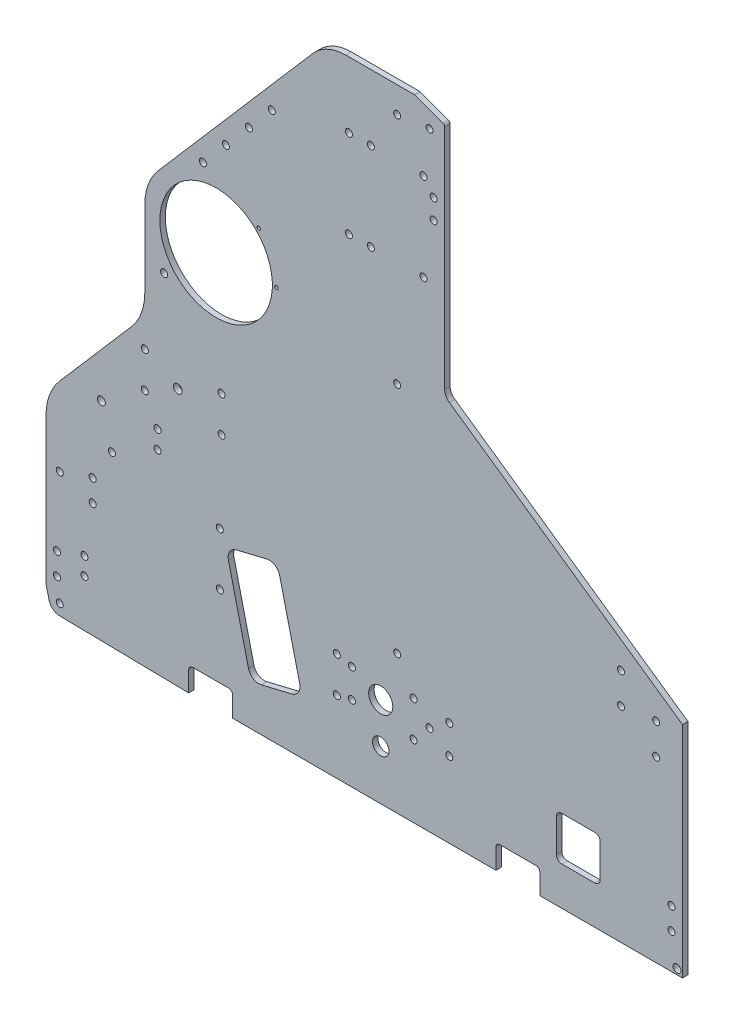
SolidWorks part; units mm, degrees
ref_plane "Front Plane" through (0, 0, 0) normal (0, 0, 1) x (1, 0, 0)
ref_plane "Top Plane" through (0, 0, 0) normal (0, 1, 0) x (1, 0, 0)
ref_plane "Right Plane" through (0, 0, 0) normal (1, 0, 0) x (0, 0, -1)
sketch "Sketch1" plane through (0, 0, 0) normal (0, 0, 1) x (1, 0, 0)
  line L0 (82.55, -20.32) -> (82.55, -6.35)
  line L2 (0, 0) -> (0, 157.48)
  line L4 (368.3, -20.32) -> (368.3, 106.68)
  line L5 (82.55, -6.35) -> (107.95, -6.35)
  line L6 (107.95, -6.35) -> (107.95, -20.32)
  line L7 (107.95, -20.32) -> (260.35, -20.32)
  line L8 (260.35, -20.32) -> (260.35, -6.35)
  line L9 (260.35, -6.35) -> (285.75, -6.35)
  line L10 (285.75, -6.35) -> (285.75, -20.32)
  line L11 (285.75, -20.32) -> (368.3, -20.32)
  line L12 (361.95, 12.7) -> (368.3, 12.7) construction
  line L13 (0, 0) -> (6.35, 0) construction
  line L14 (0.1896, -7.8901) -> (1.7771, -14.2401)
  line L15 (7.8295, -19.0491) -> (82.55, -20.32)
  line L16 (0, 0) -> (0, -6.35)
  line L17 (76.2, 128.905) -> (79.375, 128.905) construction
  line L18 (57.15, 118.5863) -> (101.6, 118.5862) construction
  line L19 (57.15, 118.5863) -> (57.15, 139.2238) construction
  line L20 (101.6, 118.5862) -> (101.6, 139.2237) construction
  line L21 (57.15, 139.2238) -> (101.6, 139.2237) construction
  line L22 (57.15, 118.5863) -> (101.6, 139.2237) construction
  line L23 (101.6, 118.5862) -> (57.15, 139.2238) construction
  line L25 (203.2, 59.805) -> (203.2, 194.805) construction
  line L26 (203.2, 194.805) -> (203.2, 329.805) construction
  line L27 (355.6, 332.105) -> (330.2, 332.105) construction
  line L28 (330.2, 332.105) -> (330.2, 217.805) construction
  line L29 (330.2, 217.805) -> (355.6, 217.805) construction
  line L30 (355.6, 217.805) -> (355.6, 332.105) construction
  line L31 (203.2, 344.805) -> (203.2, 194.805) construction
  line L32 (50.8, 332.105) -> (76.2, 332.105) construction
  line L33 (76.2, 332.105) -> (76.2, 217.805) construction
  line L34 (50.8, 217.805) -> (50.8, 332.105) construction
  line L35 (76.2, 217.805) -> (50.8, 217.805) construction
  line L36 (213.2, 344.805) -> (230.6638, 338.455)
  line L37 (203.2, 344.805) -> (161.925, 344.805)
  line L38 (203.2, 344.805) -> (213.2, 344.805)
  line L39 (348.5362, 344.805) -> (413.4623, 344.805)
  line L40 (348.5362, 344.805) -> (230.6638, 344.805) construction
  line L42 (161.925, 344.805) -> (0, 157.48)
  line L44 (230.6638, 338.455) -> (230.6638, 202.565)
  line L45 (230.6638, 202.565) -> (368.3, 106.68)
  line L46 (213.2, 344.805) -> (-141.0713, 344.805) construction
  circle A0 centre (6.35, 0) radius 2.032
  circle A1 centre (6.35, 12.7) radius 2.032
  circle A2 centre (361.95, 0) radius 2.032
  circle A3 centre (361.95, 12.7) radius 2.032
  arc A5 (1.7771, -14.2401) -> (7.8295, -19.0491) centre (7.9375, -12.7) ccw
  circle A6 centre (7.9375, -12.7) radius 2.032
  arc A7 (0, -6.35) -> (0.1896, -7.8901) centre (6.35, -6.35) ccw
  circle A8 centre (38.1, 78.105) radius 2.032
  circle A9 centre (76.2, 128.905) radius 2.54
  circle A10 centre (101.6, 118.5862) radius 2.032
  circle A11 centre (101.6, 139.2237) radius 2.032
  circle A12 centre (57.15, 139.2238) radius 2.032
  circle A13 centre (57.15, 118.5863) radius 2.032
  circle A15 centre (203.2, 59.805) radius 2
  circle A16 centre (203.2, 194.805) radius 2
  circle A17 centre (203.2, 329.805) radius 2
  circle A18 centre (63.5, 313.055) radius 2.032
  circle A20 centre (355.6, 332.105) radius 2.032
  circle A21 centre (330.2, 332.105) radius 2.032
  circle A22 centre (355.6, 217.805) radius 2.032
  circle A23 centre (330.2, 217.805) radius 2.032
  circle A24 centre (50.8, 332.105) radius 2.032
  circle A25 centre (76.2, 332.105) radius 2.032
  circle A26 centre (50.8, 217.805) radius 2.032
  circle A27 centre (76.2, 217.805) radius 2.032
  circle A28 centre (221.9319, 332.105) radius 2
  circle A29 centre (224.3138, 298.831) radius 2.032
  circle A30 centre (353.06, 100.7351) radius 2.032
  circle A31 centre (332.74, 115.9751) radius 2.032
  circle A32 centre (332.74, 98.1951) radius 2.032
  circle A33 centre (353.06, 82.9551) radius 2.032
  circle A34 centre (117.3562, 280.4276) radius 2.032
  circle A35 centre (104.0678, 265.0548) radius 2.032
  circle A36 centre (90.7795, 249.682) radius 2.032
  circle A38 centre (130.6445, 295.8004) radius 2.032
  circle A39 centre (68.326, 182.9237) radius 2.032
  circle A40 centre (224.3138, 287.401) radius 2.032
  point P82 (203.2, 344.805)
  point P83 (221.9319, 341.63)
  point P90 (368.3, 62.484)
  dimension "D6" = 4.064
  dimension "D10" = 6.35
  dimension "D11" = 4.064
  dimension "D17" = 38.1
  dimension "D27" = 4
  dimension "D31" = 4.064
  dimension "D32" = 41.275
  dimension "D36" = 4.064
  dimension "D47" = 39.624
  dimension "D48" = 4.064
  dimension "D25" = 5.08
  dimension "D26" = 4.064
  dimension "D52" = 4.064
  dimension "D65" = 4.064
  dimension "D2" = 127
  dimension "D3" = 13.97
  dimension "D4" = 25.4
  dimension "D5" = 152.4
  dimension "D7" = 12.7
  dimension "D8" = 6.35
  dimension "D9" = 20.32
  dimension "D12" = 12.7
  dimension "D13" = 1.5875
  dimension "D14" = 82.55
  dimension "D15" = 368.3
  dimension "D16" = 6.35
  dimension "D18" = 98.425
  dimension "D19" = 38.1
  dimension "D20" = 50.8
  dimension "D21" = 3.175
  dimension "D22" = 270
  dimension "D23" = 20.6375
  dimension "D24" = 44.45
  dimension "D28" = 135
  dimension "D29" = 12.7
  dimension "D30" = 15
  dimension "D33" = 63.5
  dimension "D34" = 27.4638
  dimension "D35" = 12.7
  dimension "D37" = 114.3
  dimension "D38" = 25.4
  dimension "D39" = 12.7
  dimension "D40" = 157.48
  dimension "D41" = 142.24
  dimension "D42" = 365.125
  dimension "D43" = 10
  dimension "D44" = 6.35
  dimension "D45" = 31.75
  dimension "D46" = 6.35
  dimension "D49" = 6.35
  dimension "D50" = 203.2
  dimension "D51" = 15.24
  dimension "D53" = 17.78
  dimension "D54" = 17.78
  dimension "D55" = 20.32
  dimension "D56" = 15.24
  dimension "D57" = 92.202
  dimension "D58" = 8.382
  dimension "D59" = 20.32
  dimension "D60" = 20.32
  dimension "D61" = 8.382
  dimension "D62" = 20.32
  dimension "D63" = 8.382
  dimension "D64" = 8.382
  dimension "D66" = 35.052
  dimension "D67" = 68.326
  dimension "D68" = 11.43
extrude "Boss-Extrude1" add sketch "Sketch1" along normal blind 3.175 contours L16 A7 L14 A5 L15 L2 A0 A1 A6 region at (171.3489, 119.5343, 0)
fillet "Fillet1" radius 2.286 4 edges at (285.75, -6.35, 1.5875) (107.95, -6.35, 1.5875) (260.35, -6.35, 1.5875) (82.55, -6.35, 1.5875)
fillet "Fillet2" radius 6.35 1 edges at (230.6638, 202.565, 1.5875)
sketch "Sketch2" plane through (0, 0, 0) normal (0, 0, -1) x (-1, 0, 0)
  circle A0 centre (-100.5528, 71.086) radius 2.032 construction
  circle A1 centre (-100.5528, 40.606) radius 2.032 construction
  circle A2 centre (-22.225, 18.2025) radius 2.032 construction
  circle A3 centre (-22.225, 8.0425) radius 2.032 construction
  circle A4 centre (-100.5528, 71.086) radius 2.032
  circle A5 centre (-100.5528, 40.606) radius 2.032
  circle A6 centre (-22.225, 18.2025) radius 2.032
  circle A7 centre (-22.225, 8.0425) radius 2.032
extrude "Cut-Extrude1" cut sketch "Sketch2" against normal through all
fillet "Fillet3" radius 1.5875 2 edges at (230.6638, 338.455, 1.5875) (213.2, 344.805, 1.5875)
sketch "Sketch3" plane through (0, 0, 3.175) normal (0, 0, 1) x (1, 0, 0)
  line L0 (132.9524, 63.2646) -> (132.7215, 64.2281) construction
  line L1 (128.3814, 66.8897) -> (110.6828, 62.6472) construction
  line L2 (114.5132, 58.4237) -> (126.8822, 61.3887) construction
  line L3 (108.0212, 58.3071) -> (108.2522, 57.3436) construction
  line L4 (131.2006, 57.703) -> (140.0164, 20.9265) construction
  line L5 (144.0993, 16.7636) -> (132.9524, 63.2646) construction
  line L6 (108.2522, 57.3436) -> (119.3991, 10.8426) construction
  line L7 (121.1509, 16.4042) -> (112.3351, 53.1807) construction
  line L8 (119.3991, 10.8426) -> (119.6301, 9.8791) construction
  line L9 (144.3303, 15.8001) -> (144.0993, 16.7636) construction
  line L10 (137.8383, 15.6835) -> (125.4694, 12.7185) construction
  line L11 (123.9701, 7.2175) -> (141.6687, 11.4601) construction
  line L12 (132.9524, 63.2646) -> (132.7215, 64.2281)
  line L13 (128.3814, 66.8897) -> (110.6828, 62.6472)
  line L14 (114.5132, 58.4237) -> (126.8822, 61.3887)
  line L15 (108.0212, 58.3071) -> (108.2522, 57.3436)
  line L16 (131.2006, 57.703) -> (140.0164, 20.9265)
  line L17 (144.0993, 16.7636) -> (132.9524, 63.2646)
  line L18 (108.2522, 57.3436) -> (119.3991, 10.8426)
  line L19 (121.1509, 16.4042) -> (112.3351, 53.1807)
  line L20 (119.3991, 10.8426) -> (119.6301, 9.8791)
  line L21 (144.3303, 15.8001) -> (144.0993, 16.7636)
  line L22 (137.8383, 15.6835) -> (125.4694, 12.7185)
  line L23 (123.9701, 7.2175) -> (141.6687, 11.4601)
  line L24 (127.7894, 69.3598) -> (110.0908, 65.1172)
  line L25 (105.5512, 57.715) -> (105.7822, 56.7515)
  line L26 (105.7822, 56.7515) -> (116.9291, 10.2505)
  line L27 (116.9291, 10.2505) -> (117.16, 9.287)
  line L28 (124.5622, 4.7475) -> (142.2608, 8.99)
  line L29 (146.8003, 16.3922) -> (146.5694, 17.3557)
  line L30 (146.5694, 17.3557) -> (135.4225, 63.8567)
  line L31 (135.4225, 63.8567) -> (135.1915, 64.8202)
  line L32 (14.605, -0.1369) -> (103.7278, 32.3011) construction
  line L33 (14.605, -0.1369) -> (103.7278, 32.3011)
  line L35 (-39.6666, 74.7152) -> (103.7278, 126.9065) construction
  arc A0 (132.7215, 64.2281) -> (128.6308, 66.9403) centre (129.2206, 63.3889) ccw construction
  arc A1 (110.6828, 62.6472) -> (110.4377, 62.5791) centre (111.522, 59.1463) ccw construction
  arc A2 (128.6308, 66.9403) -> (128.3814, 66.8897) centre (129.2206, 63.3889) ccw construction
  arc A3 (110.4377, 62.5791) -> (108.0212, 58.3071) centre (111.522, 59.1463) ccw construction
  arc A4 (119.6301, 9.8791) -> (123.7207, 7.1669) centre (123.1309, 10.7183) ccw construction
  arc A5 (141.9139, 11.5281) -> (144.3303, 15.8001) centre (140.8295, 14.9609) ccw construction
  arc A6 (141.6687, 11.4601) -> (141.9139, 11.5281) centre (140.8295, 14.9609) ccw construction
  arc A7 (123.7207, 7.1669) -> (123.9701, 7.2175) centre (123.1309, 10.7183) ccw construction
  arc A8 (132.7215, 64.2281) -> (128.6308, 66.9403) centre (129.2206, 63.3889) ccw
  arc A9 (110.6828, 62.6472) -> (110.4377, 62.5791) centre (111.522, 59.1463) ccw
  arc A10 (128.6308, 66.9403) -> (128.3814, 66.8897) centre (129.2206, 63.3889) ccw
  arc A11 (110.4377, 62.5791) -> (108.0212, 58.3071) centre (111.522, 59.1463) ccw
  arc A12 (119.6301, 9.8791) -> (123.7207, 7.1669) centre (123.1309, 10.7183) ccw
  arc A13 (141.9139, 11.5281) -> (144.3303, 15.8001) centre (140.8295, 14.9609) ccw
  arc A14 (141.6687, 11.4601) -> (141.9139, 11.5281) centre (140.8295, 14.9609) ccw
  arc A15 (123.7207, 7.1669) -> (123.9701, 7.2175) centre (123.1309, 10.7183) ccw
  arc A16 (110.0908, 65.1172) -> (109.6726, 65.0012) centre (111.522, 59.1463) ccw
  arc A17 (109.6726, 65.0012) -> (105.5512, 57.715) centre (111.522, 59.1463) ccw
  arc A18 (117.16, 9.287) -> (124.1369, 4.6613) centre (123.1309, 10.7183) ccw
  arc A19 (124.1369, 4.6613) -> (124.5622, 4.7475) centre (123.1309, 10.7183) ccw
  arc A20 (142.2608, 8.99) -> (142.6789, 9.1061) centre (140.8295, 14.9609) ccw
  arc A21 (142.6789, 9.1061) -> (146.8003, 16.3922) centre (140.8295, 14.9609) ccw
  arc A22 (135.1915, 64.8202) -> (128.2147, 69.446) centre (129.2206, 63.3889) ccw
  arc A23 (128.2147, 69.446) -> (127.7894, 69.3598) centre (129.2206, 63.3889) ccw
  circle A24 centre (64.5259, 102.9405) radius 2.032 construction
  circle A25 centre (64.5259, 92.5258) radius 2.032 construction
  circle A26 centre (133.35, 208.2281) radius 1.016 construction
  circle A33 centre (26.9875, 46.9531) radius 2.032
  circle A34 centre (26.9875, 59.6531) radius 2.032
  circle A35 centre (7.9375, 53.3031) radius 2.032
  circle A36 centre (7.9375, 53.3031) radius 2.032 construction
  circle A37 centre (32.0306, 100.8109) radius 31.75 construction
  circle A38 centre (32.0306, 100.8109) radius 2.286
  circle A39 centre (123.1207, 232.9238) radius 1.016 construction
  circle A40 centre (64.5259, 102.9405) radius 2.032
  circle A41 centre (64.5259, 92.5258) radius 2.032
  circle A42 centre (133.35, 208.2281) radius 1.016
  circle A43 centre (123.1207, 232.9238) radius 1.016
  circle A44 centre (26.9875, 59.6531) radius 2.032 construction
  circle A45 centre (26.9875, 46.9531) radius 2.032 construction
  ellipse E0 centre (124.5974, 48.8487) end of major axis (128.5376, 61.3578) minor radius 6 (131.2006, 57.703) -> (126.8822, 61.3887) ccw construction
  ellipse E1 centre (122.2349, 48.2824) end of major axis (113.0518, 57.6456) minor radius 6 (114.5132, 58.4237) -> (112.3351, 53.1807) ccw construction
  ellipse E2 centre (127.7541, 25.2585) end of major axis (131.6942, 37.7675) minor radius 6 (121.1509, 16.4042) -> (125.4694, 12.7185) ccw construction
  ellipse E3 centre (130.1166, 25.8248) end of major axis (139.2998, 16.4616) minor radius 6 (137.8383, 15.6835) -> (140.0164, 20.9265) ccw construction
  ellipse E4 centre (124.5974, 48.8487) end of major axis (128.5376, 61.3578) minor radius 6 (131.2006, 57.703) -> (126.8822, 61.3887) ccw
  ellipse E5 centre (122.2349, 48.2824) end of major axis (131.4181, 38.9192) minor radius 6 (114.5132, 58.4237) -> (112.3351, 53.1807) ccw
  ellipse E6 centre (127.7541, 25.2585) end of major axis (123.8139, 12.7495) minor radius 6 (121.1509, 16.4042) -> (125.4694, 12.7185) ccw
  ellipse E7 centre (130.1166, 25.8248) end of major axis (139.2998, 16.4616) minor radius 6 (137.8383, 15.6835) -> (140.0164, 20.9265) ccw
  point P115 (32.0306, 100.8109)
  dimension "D3" = 63.5
  dimension "D4" = 4.572
  dimension "D2" = 88.9
  dimension "D1" = 2.54
extrude "Cut-Extrude2" cut sketch "Sketch3" against normal through all contours A22 A23 L24 A16 A17 L25 L26 L27 A18 A19 L28 A20 A21 L29 L30 L31 A15 A12 L20 L18 L15 A11 A9 L13 A10 A8 L12 L17 L21 A13 A14 L23 | A12 A15 L23 A14 A13 L21 L17 L12 A8 A10 L13 A9 A11 L15 L18 L20 E7 L22 E6 L19 E5 L14 E4 L16 | L22 E7 L16 E4 L14 E5 L19 E6 | A38 | A41 | A40 | A35 | A34 | A33 | A43 | A42 region at (137.844, 39.8506, 3.175) region at (126.1758, 37.0536, 3.175) region at (128.1544, 68.6507, 3.175) region at (32.0306, 100.8109, 3.175) region at (64.5259, 102.9405, 3.175) region at (64.5259, 92.5258, 3.175)
sketch "Sketch4" plane through (0, 0, 3.175) normal (0, 0, 1) x (1, 0, 0)
  line L0 (57.15, 139.2238) -> (101.6, 139.2237) construction
  line L1 (168.275, 21.4312) -> (212.725, 21.4312) construction
  line L2 (168.275, 21.4312) -> (168.275, 42.0687) construction
  line L3 (168.275, 42.0687) -> (212.725, 42.0687) construction
  line L4 (212.725, 21.4312) -> (212.725, 42.0687) construction
  line L5 (168.275, 21.4312) -> (212.725, 42.0687) construction
  line L6 (168.275, 42.0687) -> (212.725, 21.4312) construction
  line L7 (57.15, 118.5863) -> (57.15, 139.2238) construction
  line L8 (107.95, -20.32) -> (260.35, -20.32) construction
  line L9 (193.675, 31.75) -> (177.005, 31.75) construction
  line L10 (190.5, 31.75) -> (193.675, 31.75) construction
  line L11 (6.35, 12.7) -> (361.95, 12.7) construction
  line L12 (107.95, -6.35) -> (107.95, -20.32) construction
  line L13 (193.675, 31.75) -> (220.6625, 31.75) construction
  line L14 (177.005, 23.4569) -> (177.005, 40.0431) construction
  line L15 (213.2, 44.805) -> (193.2, 44.805) construction
  line L16 (213.2, 44.805) -> (213.2, 344.805) construction
  line L17 (213.2, 344.805) -> (193.2, 344.805) construction
  line L18 (193.2, 44.805) -> (193.2, 344.805) construction
  line L19 (213.2, 44.805) -> (193.2, 344.805) construction
  line L20 (213.2, 344.805) -> (193.2, 44.805) construction
  line L21 (226.9319, 332.105) -> (226.9319, 31.75) construction
  line L22 (237.33, 40.0431) -> (233.3612, 40.0431) construction
  line L23 (237.33, 23.4569) -> (233.3612, 23.4569) construction
  circle A0 centre (168.275, 42.0687) radius 2.032
  circle A1 centre (212.725, 42.0687) radius 2.032
  circle A2 centre (212.725, 21.4312) radius 2.032
  circle A3 centre (168.275, 21.4312) radius 2.032
  circle A4 centre (193.675, 31.75) radius 6.985
  circle A7 centre (220.6625, 31.75) radius 14.2875 construction
  circle A8 centre (193.675, 31.75) radius 12.7 construction
  circle A9 centre (177.005, 40.0431) radius 2.032
  circle A10 centre (177.005, 23.4569) radius 2.032
  circle A11 centre (237.33, 40.0431) radius 2.032 construction
  circle A12 centre (237.33, 23.4569) radius 2.032 construction
  circle A13 centre (193.675, 8.4667) radius 4.7625
  circle A14 centre (221.9319, 31.75) radius 2.032
  circle A15 centre (221.9319, 31.75) radius 5 construction
  circle A16 centre (221.9319, 332.105) radius 5 construction
  circle A17 centre (233.3612, 23.4569) radius 2.032
  circle A18 centre (233.3612, 40.0431) radius 2.032
  point P0 (190.5, 31.75)
  point P26 (203.2, 194.805)
  point P38 (177.005, 31.75)
  dimension "D1" = 4.064
  dimension "D4" = 13.97
  dimension "D7" = 9.525
  dimension "D10" = 25.4
  dimension "D11" = 28.575
  dimension "D16" = 10
  dimension "D17" = 4.064
  dimension "D18" = 10
  dimension "D2" = 52.07
  dimension "D3" = 3.175
  dimension "D5" = 82.55
  dimension "D6" = 26.9875
  dimension "D8" = 20
  dimension "D9" = 300
  dimension "D12" = 16.67
  dimension "D13" = 16.5862
  dimension "D14" = 60.325
  dimension "D15" = 23.2833
  dimension "D19" = 3.9688
extrude "Cut-Extrude3" cut sketch "Sketch4" against normal through all
sketch "Sketch5" plane through (0, 0, -187.325) normal (0, 0, -1) x (-1, 0, 0)
  line L0 (-57.15, 223.5947) -> (-57.15, 155.6235)
  line L1 (-161.925, 344.805) -> (-52.7201, 218.4699) construction
  line L2 (-57.15, 155.6235) -> (0, 89.5088)
  line L3 (0, -6.35) -> (0, 157.48) construction
  line L4 (-50.4199, 215.8089) -> (0, 157.48) construction
  line L5 (-50.4199, 215.8089) -> (0, 157.48) construction
  line L6 (-57.15, 223.5947) -> (0, 157.48)
  line L7 (0, 157.48) -> (0, 89.5088)
  circle A0 centre (-98.425, 208.2281) radius 32.5437
  circle A1 centre (-365.125, -17.145) radius 2.286 construction
  circle A2 centre (-365.125, -17.145) radius 2.286
  dimension "D3" = 65.0875
  dimension "D1" = 44.45
  dimension "D2" = 57.15
  dimension "D4" = 41.275
  dimension "D5" = 41.275
extrude "Cut-Extrude5" cut sketch "Sketch5" against normal through all contours A0 | L7 L6 L0 L2 | A2 region at (28.575, 156.5518, -187.325) region at (98.425, 208.2281, -187.325)
fillet "Fillet4" radius 31.75 3 edges at (0, 89.5088, 1.5875) (57.15, 155.6235, 1.5875) (57.15, 223.5947, 1.5875)
sketch "Sketch6" plane through (0, 0, 3.175) normal (0, 0, 1) x (1, 0, 0)
  line L0 (285.75, -20.32) -> (368.3, -20.32) construction
  line L1 (298.45, 27.305) -> (317.5, 27.305)
  line L2 (295.275, 24.13) -> (295.275, 5.08)
  line L3 (298.45, 1.905) -> (317.5, 1.905)
  line L4 (320.675, 24.13) -> (320.675, 5.08)
  line L5 (295.275, 27.305) -> (320.675, 1.905) construction
  line L6 (295.275, 1.905) -> (320.675, 27.305) construction
  line L7 (368.3, -20.32) -> (368.3, 106.68) construction
  arc A0 (295.275, 5.08) -> (298.45, 1.905) centre (298.45, 5.08) ccw
  arc A1 (317.5, 1.905) -> (320.675, 5.08) centre (317.5, 5.08) ccw
  arc A2 (317.5, 27.305) -> (320.675, 24.13) centre (317.5, 24.13) cw
  arc A3 (298.45, 27.305) -> (295.275, 24.13) centre (298.45, 24.13) ccw
  point P0 (307.975, 14.605)
  dimension "D2" = 3.175
  dimension "D1" = 25.4
  dimension "D3" = 22.225
  dimension "D4" = 47.625
extrude "Cut-Extrude6" cut sketch "Sketch6" against normal through all
fillet "Fillet5" radius 25.4 1 edges at (161.925, 344.805, 1.5875)
sketch "Sketch8" plane through (0, 0, 0) normal (0, 0, -1) x (-1, 0, 0)
  circle A0 centre (-187.96, 306.705) radius 2.032 construction
  arc A1 (-176.3652, 304.9998) -> (-176.3652, 308.4102) centre (-175.26, 306.705) ccw construction
  arc A2 (-219.0586, 304.7694) -> (-219.0586, 308.6405) centre (-218.44, 306.705) ccw construction
  circle A3 centre (-205.74, 306.705) radius 2.032 construction
  arc A4 (-219.0586, 253.9694) -> (-219.0586, 257.8405) centre (-218.44, 255.905) ccw construction
  circle A5 centre (-205.74, 255.905) radius 2.032 construction
  circle A6 centre (-187.96, 255.905) radius 2.032 construction
  arc A7 (-176.3652, 254.1998) -> (-176.3652, 257.6102) centre (-175.26, 255.905) ccw construction
  circle A8 centre (-187.96, 306.705) radius 2.032
  arc A9 (-176.3652, 304.9998) -> (-176.3652, 308.4102) centre (-175.26, 306.705) ccw
  arc A10 (-219.0586, 304.7694) -> (-219.0586, 308.6405) centre (-218.44, 306.705) ccw
  circle A11 centre (-205.74, 306.705) radius 2.032
  arc A12 (-219.0586, 253.9694) -> (-219.0586, 257.8405) centre (-218.44, 255.905) ccw
  circle A13 centre (-205.74, 255.905) radius 2.032
  circle A14 centre (-187.96, 255.905) radius 2.032
  arc A15 (-176.3652, 254.1998) -> (-176.3652, 257.6102) centre (-175.26, 255.905) ccw
  circle A16 centre (-218.44, 306.705) radius 2.032
  circle A17 centre (-175.26, 306.705) radius 2.032
  circle A18 centre (-175.26, 255.905) radius 2.032
  circle A19 centre (-218.44, 255.905) radius 2.032
  circle A20 centre (-218.44, 306.705) radius 3.9687
  circle A21 centre (-205.74, 306.705) radius 3.9687
  circle A22 centre (-175.26, 306.705) radius 3.9687
  circle A23 centre (-218.44, 255.905) radius 3.9687
  circle A24 centre (-205.74, 255.905) radius 3.9687
  circle A25 centre (-187.96, 255.905) radius 3.9687
  circle A26 centre (-175.26, 255.905) radius 3.9687
  circle A27 centre (-187.96, 306.705) radius 3.9687
  dimension "D1" = 7.9375
extrude "Cut-Extrude7" cut sketch "Sketch8" against normal through all contours A10 A16 | A9 A17 | A15 A18 | A12 A19 | A8 | A14 region at (175.26, 306.705, 0) region at (218.44, 306.705, 0) region at (218.44, 255.905, 0) region at (175.26, 255.905, 0)
